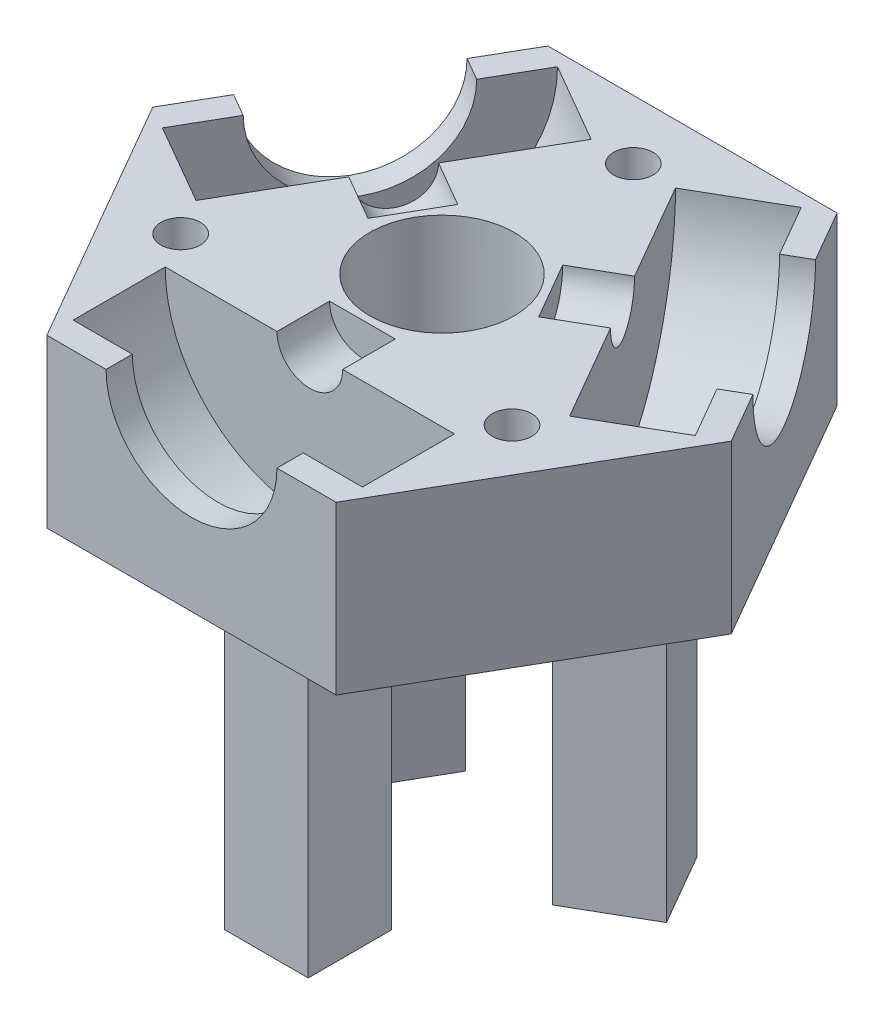
SolidWorks part; units mm, degrees
ref_plane "Front Plane" through (0, 0, 0) normal (0, 0, 1) x (1, 0, 0)
ref_plane "Top Plane" through (0, 0, 0) normal (0, 1, 0) x (1, 0, 0)
ref_plane "Right Plane" through (0, 0, 0) normal (1, 0, 0) x (0, 0, -1)
sketch "Sketch1" plane through (0, 0, 0) normal (0, 1, 0) x (1, 0, 0)
  line L1 (11, -19.0526) -> (22, 0)
  line L2 (22, 0) -> (11, 19.0526)
  line L3 (11, 19.0526) -> (-11, 19.0526)
  line L4 (-11, 19.0526) -> (-22, 0)
  line L5 (-22, 0) -> (-11, -19.0526)
  line L6 (-11, -19.0526) -> (11, -19.0526)
  circle A0 centre (0, 0) radius 19.0526 construction
  dimension "D1" = 22
extrude "Boss-Extrude1" add sketch "Sketch1" along normal blind 12.7 contours L4 L5 L6 L1 L2 L3
sketch "Sketch2" plane through (0, 0, 0) normal (0, -1, 0) x (1, 0, 0)
  circle A0 centre (0, 0) radius 5.5
  circle A1 centre (0, 0) radius 8.5
  dimension "D1" = 11
  dimension "D2" = 3
extrude "Boss-Extrude2" add sketch "Sketch2" along normal blind 3.5
sketch "Sketch4" plane through (0, 0, 0) normal (0, -1, 0) x (1, 0, 0)
  line L0 (13.1489, -3.9254) -> (7.6497, -0.7504)
  line L1 (-3.175, 13.35) -> (3.175, 13.35)
  line L2 (-3.175, 13.35) -> (-3.175, 7)
  line L3 (-3.175, 7) -> (3.175, 7)
  line L4 (3.175, 13.35) -> (3.175, 7)
  line L5 (-3.175, 13.35) -> (3.175, 7) construction
  line L6 (-3.175, 7) -> (3.175, 13.35) construction
  line L7 (13.1489, -3.9254) -> (9.9739, -9.4246)
  line L8 (9.9739, -9.4246) -> (4.4747, -6.2496)
  line L9 (7.6497, -0.7504) -> (4.4747, -6.2496)
  line L10 (-9.9739, -9.4246) -> (-4.4747, -6.2496)
  line L11 (-9.9739, -9.4246) -> (-13.1489, -3.9254)
  line L12 (-13.1489, -3.9254) -> (-7.6497, -0.7504)
  line L13 (-4.4747, -6.2496) -> (-7.6497, -0.7504)
  circle A1 centre (0, 0) radius 5.5 construction
  circle A2 centre (0, 0) radius 5.5 construction
  point P0 (0, 10.175)
  point P18 (0, 0)
  dimension "D1" = 6.35
  dimension "D2" = 1.5
  dimension "D4" = 1.5
  dimension "D5" = 1.5
  dimension "D3" = 3
extrude "Boss-Extrude4" add sketch "Sketch4" along normal blind 25.4
sketch "Sketch5" plane through (0, 12.7, 0) normal (0, 1, 0) x (1, 0, 0)
  line L14 (0, -19.0526) -> (0, -6.0526)
  line L15 (-11, -19.0526) -> (11, -19.0526) construction
  line L16 (0, -6.0526) -> (-2.5, -6.0526)
  line L17 (-2.5, -6.0526) -> (-2.5, -10.0526)
  line L18 (-2.5, -10.0526) -> (-11, -10.0526)
  line L19 (-11, -10.0526) -> (-11, -17.0526)
  line L20 (-11, -17.0526) -> (-6.5, -17.0526)
  line L21 (-6.5, -17.0526) -> (-6.5, -19.0526)
  line L22 (-6.5, -19.0526) -> (0, -19.0526)
  dimension "D1" = 6.5
  dimension "D2" = 11
  dimension "D3" = 2
  dimension "D4" = 7
  dimension "D5" = 4
  dimension "D6" = 2.5
revolve "Cut-Revolve1" cut sketch "Sketch5" angle 360 about L14
pattern_circular "CirPattern1" count 3 over 360 about axis through (0, -3.5, 0) along (0, 1, 0) of "Cut-Revolve1" reverse direction yes
sketch "Sketch6" plane through (0, 12.7, 0) normal (0, 1, 0) x (1, 0, 0)
  circle A0 centre (0, 0) radius 5.5
  dimension "D1" = 11
extrude "Cut-Extrude1" cut sketch "Sketch6" against normal through all
sketch "Sketch7" plane through (0, 12.7, 0) normal (0, 1, 0) x (1, 0, 0)
  line L0 (11, 19.0526) -> (-11, 19.0526) construction
  line L1 (-22, 0) -> (-11, -19.0526) construction
  line L2 (11, -19.0526) -> (22, 0) construction
  circle A0 centre (0, 14.5526) radius 1.5
  circle A1 centre (12.6029, -7.2763) radius 1.5
  circle A2 centre (-12.6029, -7.2763) radius 1.5
  point P11 (0, 0)
  dimension "D1" = 3
  dimension "D2" = 3
  dimension "D4" = 3
  dimension "D5" = 3
  dimension "D3" = 3
extrude "Cut-Extrude2" cut sketch "Sketch7" against normal up to surface (12.7 mm away) up to face at (0, 0, 0)
